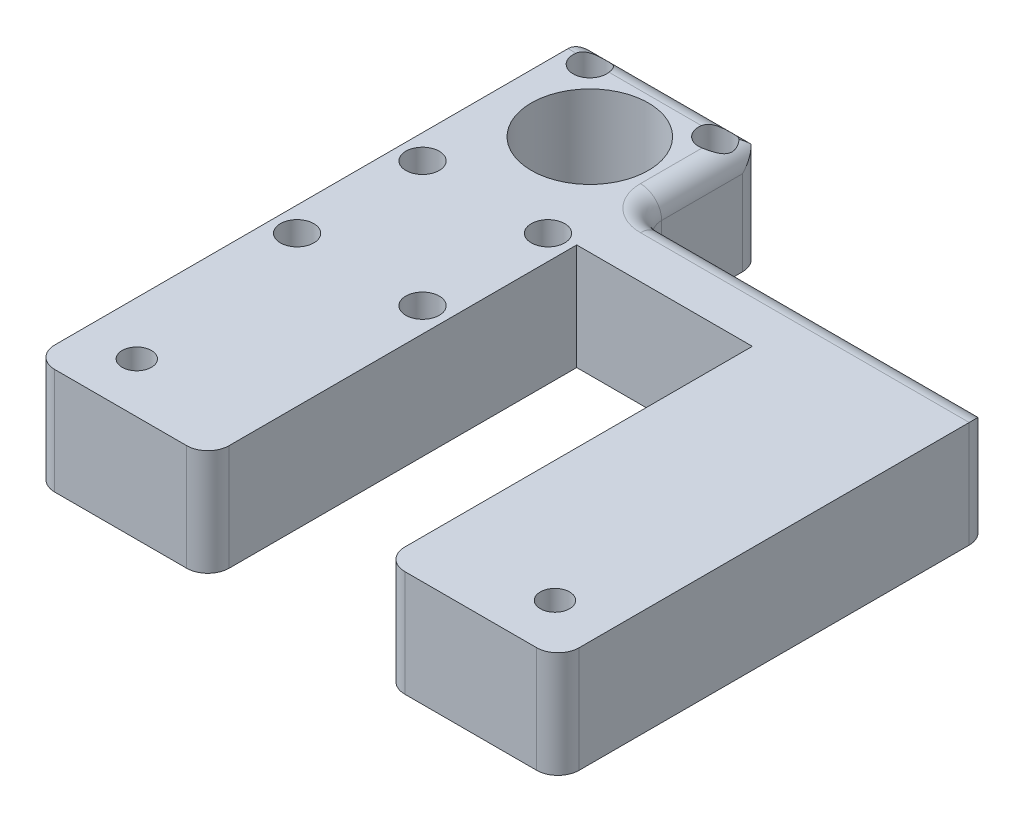
SolidWorks part; units mm, degrees
material "PLA"
ref_plane "Front Plane" through (0, 0, 0) normal (0, 0, 1) x (1, 0, 0)
ref_plane "Top Plane" through (0, 0, 0) normal (0, 1, 0) x (1, 0, 0)
ref_plane "Right Plane" through (0, 0, 0) normal (1, 0, 0) x (0, 0, -1)
sketch "Sketch1" plane through (0, 0, 0) normal (0, 1, 0) x (1, 0, 0)
  line L0 (-31.35, -25.86) -> (-31.35, 25.86)
  line L1 (-31.35, 25.86) -> (31.35, 25.86)
  line L2 (31.35, 25.86) -> (31.35, -25.86)
  line L3 (31.35, -25.86) -> (10.5, -25.86)
  line L4 (10.5, -25.86) -> (10.5, 18.24)
  line L5 (10.5, 18.24) -> (-10.5, 18.24)
  line L6 (-10.5, 18.24) -> (-10.5, -25.86)
  line L7 (-10.5, -25.86) -> (-31.35, -25.86)
  line L8 (-25, -19.86) -> (25, -19.86) construction
  circle A0 centre (-25, -19.86) radius 1.75
  circle A1 centre (25, -19.86) radius 1.75
  point P2 (0, 18.24)
  point P11 (31.35, 0)
  point P15 (0, -19.86)
  dimension "D5" = 3.5
  dimension "D1" = 21
  dimension "D2" = 50
  dimension "D3" = 38.1
  dimension "D4" = 6
  dimension "D6" = 6.35
  dimension "D7" = 7.62
extrude "Boss-Extrude1" add sketch "Sketch1" along normal mid plane 12.7
sketch "Sketch5" plane through (0, -6.35, 0) normal (0, -1, 0) x (1, 0, 0)
  line L0 (-10.5, 25.86) -> (-10.5, -18.24) construction
  line L1 (-31.35, -25.86) -> (-10.5, -25.86)
  line L2 (-31.35, -25.86) -> (-31.35, -40.592)
  line L3 (-31.35, -40.592) -> (-10.5, -40.592)
  line L4 (-10.5, -25.86) -> (-10.5, -40.592)
  dimension "D1" = 14.732
extrude "Boss-Extrude2" add sketch "Sketch5" against normal through all
sketch "Sketch2" plane through (0, 6.35, 0) normal (0, 1, 0) x (1, 0, 0)
  line L1 (-28.425, 2.732) -> (-13.425, 2.732) construction
  line L2 (-28.425, 2.732) -> (-28.425, 17.732) construction
  line L3 (-28.425, 17.732) -> (-13.425, 17.732) construction
  line L4 (-13.425, 2.732) -> (-13.425, 17.732) construction
  line L5 (-28.425, 2.732) -> (-13.425, 17.732) construction
  line L6 (-28.425, 17.732) -> (-13.425, 2.732) construction
  line L7 (-31.35, -25.86) -> (-10.5, -25.86) construction
  line L8 (31.35, 25.86) -> (-10.5, 25.86) construction
  line L9 (-28.425, 17.732) -> (-28.425, 37.732) construction
  line L10 (-28.425, 37.732) -> (-13.425, 37.732) construction
  line L11 (-13.425, 37.732) -> (-13.425, 17.732) construction
  circle A0 centre (-28.425, 17.732) radius 1.125
  circle A1 centre (-13.425, 17.732) radius 1.125
  circle A2 centre (-13.425, 2.732) radius 1.125
  circle A3 centre (-28.425, 2.732) radius 1.125
  circle A4 centre (-13.425, 37.732) radius 1.125
  circle A5 centre (-28.425, 37.732) radius 1.125
  point P0 (-20.925, 10.232)
  point P15 (-20.925, -25.86)
  point P16 (-20.925, 2.732)
  dimension "D2" = 2.25
  dimension "D1" = 15
  dimension "D3" = 8.128
  dimension "D4" = 20
  dimension "D5" = 15
extrude "Cut-Extrude1" cut sketch "Sketch2" against normal through all
sketch "Sketch3" plane through (0, 6.35, 0) normal (0, 1, 0) x (1, 0, 0)
  circle A0 centre (-28.425, 17.732) radius 2
  circle A1 centre (-13.425, 17.732) radius 2
  circle A2 centre (-13.425, 2.732) radius 2
  circle A3 centre (-28.425, 2.732) radius 2
  circle A4 centre (-28.425, 37.732) radius 2
  circle A5 centre (-13.425, 37.732) radius 2
  dimension "D1" = 4
extrude "Cut-Extrude2" cut sketch "Sketch3" against normal blind 11.2
fillet "Fillet1" radius 2.54 9 edges at (-31.35, 0, 25.86) (31.35, 0, -25.86) (31.35, 0, 25.86) (10.5, 0, 25.86) (-10.5, 0, 25.86) (10.425, 6.35, -25.86) (-31.35, 0, -40.592) (-10.5, 0, -25.86) (-10.5, 0, -40.592)
fillet "Fillet2" radius 2.54 1 edges at (-20.925, 6.35, -40.592)
sketch "Sketch6" plane through (0, 6.35, 0) normal (0, 1, 0) x (1, 0, 0)
  line L0 (-28.425, 17.732) -> (-13.425, 17.732) construction
  circle A0 centre (-20.925, 30.232) radius 7
  circle A1 centre (-13.425, 2.732) radius 1.125 construction
  point P2 (-20.925, 17.732)
  dimension "D1" = 14
  dimension "D2" = 27.5
extrude "Cut-Extrude3" cut sketch "Sketch6" against normal through all
